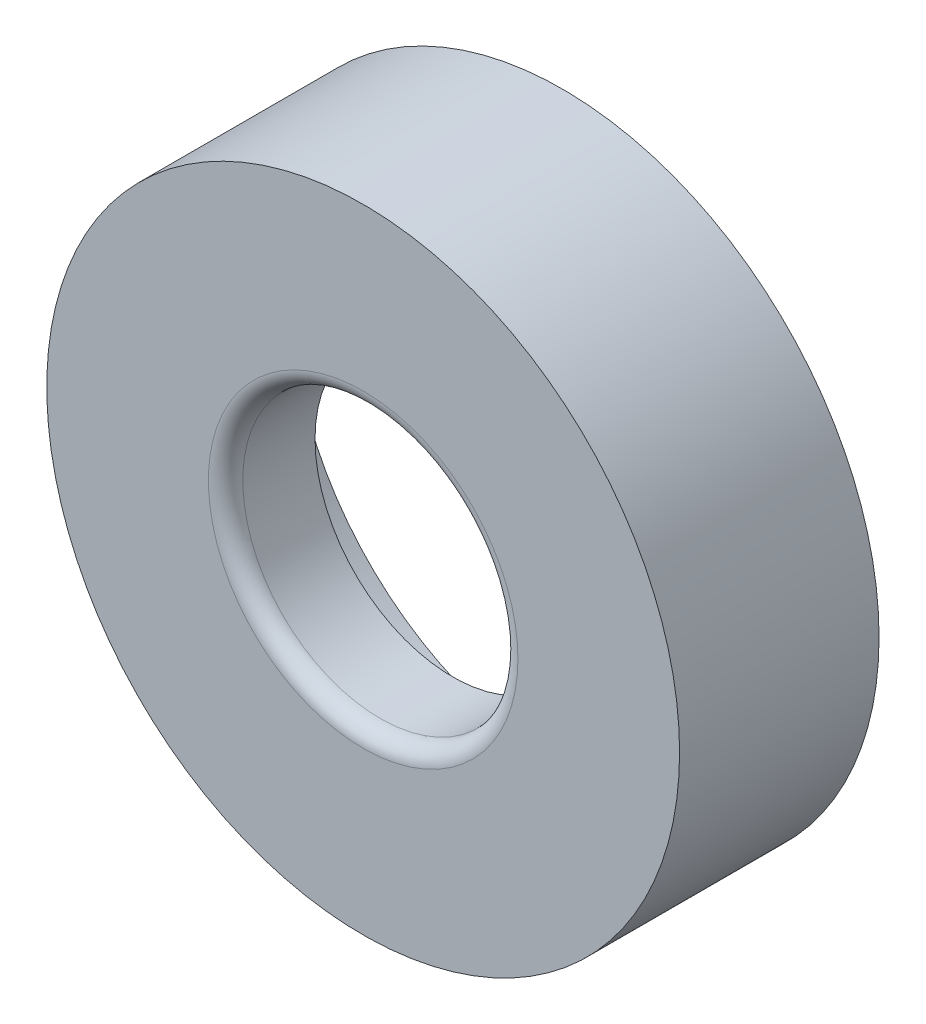
SolidWorks part; units mm, degrees
ref_plane "Front Plane" through (0, 0, 0) normal (0, 0, 1) x (1, 0, 0)
ref_plane "Top Plane" through (0, 0, 0) normal (0, 1, 0) x (1, 0, 0)
ref_plane "Right Plane" through (0, 0, 0) normal (1, 0, 0) x (0, 0, -1)
sketch "Sketch1" plane through (0, 0, 0) normal (0, 0, 1) x (1, 0, 0)
  circle A0 centre (85.2065, -1.764) radius 9.2
  dimension "D1" = 18.4
extrude "Boss-Extrude1" add sketch "Sketch1" along normal blind 5.8
sketch "Sketch2" plane through (0, 0, 5.8) normal (0, 0, 1) x (1, 0, 0)
  circle A0 centre (85.2065, -1.764) radius 4
  dimension "D1" = 8
extrude "Cut-Extrude1" cut sketch "Sketch2" against normal through all
sketch "Sketch3" plane through (0, 0, 0) normal (0, 0, -1) x (-1, 0, 0)
  circle A0 centre (-85.2065, -1.764) radius 7.9
  dimension "D1" = 15.8
extrude "Cut-Extrude2" cut sketch "Sketch3" against normal blind 3.2
fillet "Fillet1" radius 0.5 1 edges at (89.2065, -1.764, 5.8)
